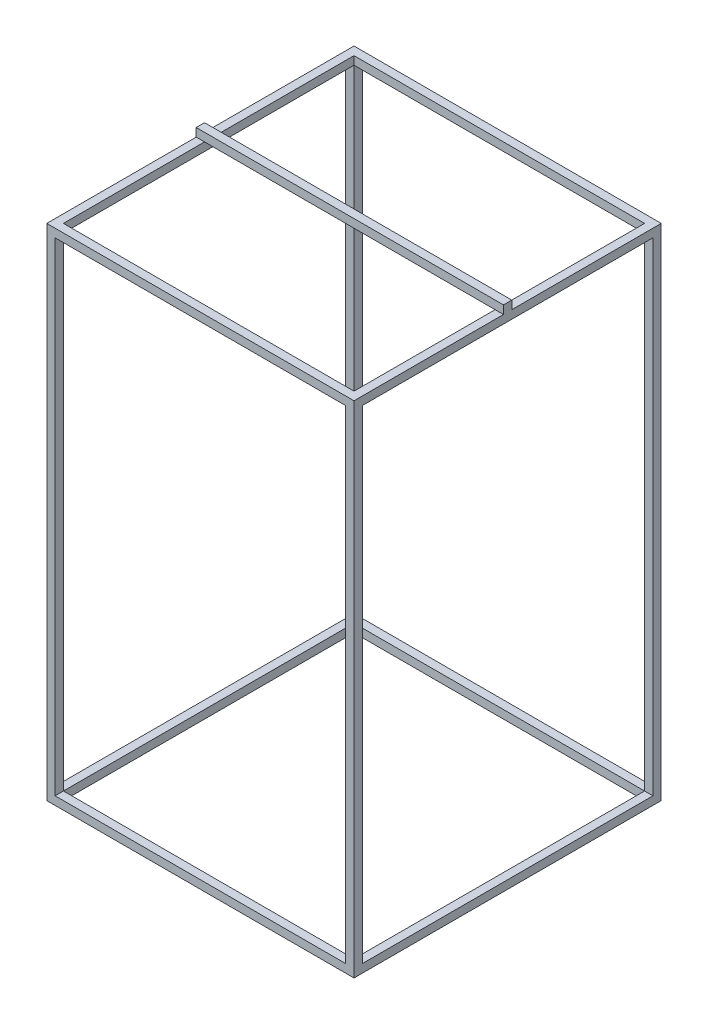
SolidWorks part; units mm, degrees
ref_plane "Front Plane" through (0, 0, 0) normal (0, 0, 1) x (1, 0, 0)
ref_plane "Top Plane" through (0, 0, 0) normal (0, 1, 0) x (1, 0, 0)
ref_plane "Right Plane" through (0, 0, 0) normal (1, 0, 0) x (0, 0, -1)
sketch "Sketch2" plane through (0, 0, 0) normal (0, 1, 0) x (1, 0, 0)
  line L0 (-720.725, 0) -> (720.725, 0) construction
  line L1 (-762, -762) -> (762, -762)
  line L2 (-762, -762) -> (-762, 762)
  line L3 (-762, 762) -> (762, 762)
  line L4 (762, -762) -> (762, 762)
  line L5 (-762, -762) -> (762, 762) construction
  line L6 (-762, 762) -> (762, -762) construction
  line L7 (-720.725, -720.725) -> (720.725, -720.725)
  line L8 (-720.725, -720.725) -> (-720.725, 720.725)
  line L9 (-720.725, 720.725) -> (720.725, 720.725)
  line L10 (720.725, -720.725) -> (720.725, 720.725)
  line L11 (-720.725, -720.725) -> (720.725, 720.725) construction
  line L12 (-720.725, 720.725) -> (720.725, -720.725) construction
  line L13 (762, 762) -> (720.725, 762)
  line L14 (762, 762) -> (762, 720.725)
  line L15 (762, 720.725) -> (720.725, 720.725)
  line L16 (720.725, 762) -> (720.725, 720.725)
  line L17 (0, 720.725) -> (0, -720.725) construction
  line L19 (-762, 762) -> (-720.725, 762)
  line L20 (-762, 762) -> (-762, 720.725)
  line L21 (-762, 720.725) -> (-720.725, 720.725)
  line L22 (-720.725, 762) -> (-720.725, 720.725)
  line L23 (762, -762) -> (720.725, -762)
  line L24 (762, -762) -> (762, -720.725)
  line L25 (762, -720.725) -> (720.725, -720.725)
  line L26 (720.725, -762) -> (720.725, -720.725)
  line L27 (-762, -762) -> (-720.725, -762)
  line L28 (-762, -762) -> (-762, -720.725)
  line L29 (-762, -720.725) -> (-720.725, -720.725)
  line L30 (-720.725, -762) -> (-720.725, -720.725)
  point P0 (0, 0)
  point P6 (0, 0)
  dimension "D1" = 41.275
  dimension "D2" = 1524
  dimension "D3" = 1524
extrude "Boss-Extrude1" add sketch "Sketch2" along normal blind 41.275 contours L3 L22 L9 L16 | L3 L16 L15 L4 | L25 L4 L15 L10 | L26 L1 L4 L25 | L30 L1 L26 L7 | L1 L30 L29 L2 | L2 L29 L8 L21 | L22 L3 L2 L21 region at (-741.3625, 0, 741.3625) region at (0, 0, 741.3625) region at (-741.3625, 0, 0) region at (741.3625, 0, 741.3625) region at (-741.3625, 0, -741.3625) region at (741.3625, 0, 0) region at (0, 0, -741.3625) region at (741.3625, 0, -741.3625)
extrude "Boss-Extrude2" add sketch "Sketch2<4>" along normal blind 2438.4 contours L22 L3 L2 L21 | L3 L16 L15 L4 | L26 L1 L4 L25 | L1 L30 L29 L2 region at (-741.3625, 0, 741.3625) region at (741.3625, 0, 741.3625) region at (-741.3625, 0, -741.3625) region at (741.3625, 0, -741.3625)
sketch "Sketch2<4>" plane through (0, 0, 0) normal (0, 1, 0) x (1, 0, 0) same geometry as "Sketch2"
extrude "Boss-Extrude3" add sketch "Sketch2<5>" along normal blind 41.275 from surface contours L1 L30 L29 L2 | L22 L3 L2 L21 | L2 L29 L8 L21 | L3 L22 L9 L16 | L3 L16 L15 L4 | L25 L4 L15 L10 | L26 L1 L4 L25 | L30 L1 L26 L7 region at (-741.3625, 0, 741.3625) region at (0, 0, 741.3625) region at (-741.3625, 0, 0) region at (741.3625, 0, 741.3625) region at (-741.3625, 0, -741.3625) region at (741.3625, 0, 0) region at (0, 0, -741.3625) region at (741.3625, 0, -741.3625) starting at face at (-741.3625, 2438.4, 741.3625)
sketch "Sketch2<5>" plane through (0, 0, 0) normal (0, 1, 0) x (1, 0, 0) same geometry as "Sketch2"
sketch "Sketch3" plane through (0, 2479.675, 0) normal (0, 1, 0) x (1, 0, 0)
  line L0 (762, 762) -> (762, -762) construction
  line L1 (-762, -20.6375) -> (762, -20.6375)
  line L2 (-762, -20.6375) -> (-762, 20.6375)
  line L3 (-762, 20.6375) -> (762, 20.6375)
  line L4 (762, -20.6375) -> (762, 20.6375)
  line L5 (-762, -20.6375) -> (762, 20.6375) construction
  line L6 (-762, 20.6375) -> (762, -20.6375) construction
  point P0 (0, 0)
  dimension "D1" = 41.275
extrude "Boss-Extrude4" add sketch "Sketch3" along normal blind 41.275
